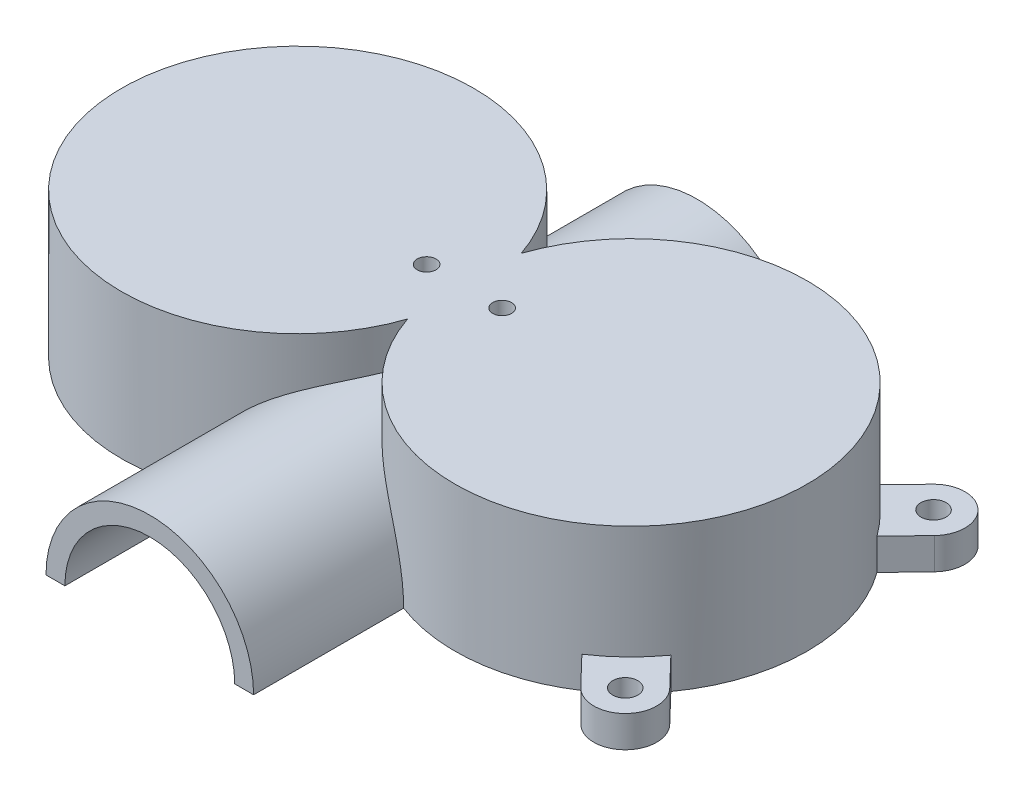
SolidWorks part; units mm, degrees
ref_plane "Front Plane" through (0, 0, 0) normal (0, 0, 1) x (1, 0, 0)
ref_plane "Top Plane" through (0, 0, 0) normal (0, 1, 0) x (1, 0, 0)
ref_plane "Right Plane" through (0, 0, 0) normal (1, 0, 0) x (0, 0, -1)
sketch "Sketch1" plane through (0, 0, 0) normal (0, 1, 0) x (1, 0, 0)
  line L0 (-26.5, 0) -> (26.5, 0) construction
  arc A0 (0, 9.0416) -> (0, -9.0416) centre (-26.5, 0) ccw
  arc A1 (0, -9.0416) -> (0, 9.0416) centre (26.5, 0) ccw
  dimension "D2" = 56
  dimension "D1" = 53
extrude "Boss-Extrude1" add sketch "Sketch1" along normal blind 23 contours A0 A1
shell "Shell1" [suppressed] thickness 3
sketch "Sketch2" plane through (0, 0, 0) normal (0, 1, 0) x (1, 0, 0)
  line L0 (-33.5, 33) -> (-33.5, 27.1109)
  line L1 (-23.5, 33) -> (-23.5, 27.8388)
  circle A0 centre (-28.5, 33) radius 2
  arc A1 (-23.5, 33) -> (-33.5, 33) centre (-28.5, 33) ccw
  arc A2 (-23.5, 27.8388) -> (-33.5, 27.1109) centre (-26.5, 0) ccw
  point P2 (0, 0)
  dimension "D3" = 4
  dimension "D4" = 10
  dimension "D5" = 56
  dimension "D1" = 33
  dimension "D2" = 28.5
  dimension "D6" = 26.5
extrude "Boss-Extrude2" add sketch "Sketch2" along normal blind 5
sketch "Sketch3" plane through (0, 0, 0) normal (0, 1, 0) x (1, 0, 0)
  line L0 (50.0744, 24.5) -> (50.0744, -24.5) construction
  line L1 (26.5, 0) -> (50.0744, -24.5) construction
  line L2 (0, 0) -> (50.0744, 0) construction
  line L3 (50.0744, 24.5) -> (26.5, 0) construction
  line L4 (46.4714, -27.9668) -> (41.9992, -23.319)
  line L5 (53.6773, -21.0332) -> (49.2051, -16.3854)
  line L6 (46.4714, 27.9668) -> (41.9992, 23.319)
  line L7 (53.6773, 21.0332) -> (49.2051, 16.3854)
  circle A0 centre (50.0744, 24.5) radius 2
  circle A1 centre (50.0744, -24.5) radius 2
  arc A2 (50.0744, 15.1079) -> (41.9992, 23.319) centre (26.5, 0) ccw
  arc A3 (53.6773, 21.0332) -> (46.4714, 27.9668) centre (50.0744, 24.5) ccw
  arc A4 (46.4714, -27.9668) -> (53.6773, -21.0332) centre (50.0744, -24.5) ccw
  arc A6 (41.9992, -23.319) -> (50.0744, -15.1079) centre (26.5, 0) ccw
  dimension "D3" = 56
  dimension "D5" = 4
  dimension "D6" = 10
  dimension "D1" = 49
  dimension "D2" = 26.5
  dimension "D4" = 34
extrude "Boss-Extrude3" add sketch "Sketch3" along normal blind 5 contours L7 A3 L6 A2 A0 | A6 L4 A4 L5 A1 region at (44.3687, 0, 25.5145) region at (53.4128, 0, -27.9695)
sketch "Sketch6" plane through (0, 0, 0) normal (0, 0, 1) x (1, 0, 0)
  line L0 (-16.5, 0) -> (16.5, 0)
  arc A0 (16.5, 0) -> (-16.5, 0) centre (0, 0) ccw
  dimension "D1" = 33
extrude "Boss-Extrude4" add sketch "Sketch6" against normal blind 37
extrude "Boss-Extrude5" add sketch "Sketch6<2>" along normal blind 50
sketch "Sketch6<2>" plane through (0, 0, 0) normal (0, 0, 1) x (1, 0, 0) same geometry as "Sketch6"
sketch "Sketch4" plane through (0, 0, 0) normal (0, 0, 1) x (1, 0, 0)
  line L0 (-13.5, 0) -> (13.5, 0)
  arc A0 (13.5, 0) -> (-13.5, 0) centre (0, 0) ccw
  dimension "D1" = 27
extrude "Cut-Extrude1" cut sketch "Sketch4" against normal through all both and the other way through all
sketch "Sketch5" plane through (0, 0, 0) normal (0, 1, 0) x (1, 0, 0)
  line L0 (26.5, 0) -> (-26.5, 0) construction
  circle A0 centre (-26.5, 0) radius 25
  circle A1 centre (26.5, 0) radius 25
  dimension "D2" = 50
  dimension "D1" = 53
extrude "Cut-Extrude4" cut sketch "Sketch5" along normal blind 20
sketch "Sketch7" plane through (0, 0, 0) normal (0, 1, 0) x (1, 0, 0)
  line L0 (-6, 0) -> (6, 0) construction
  circle A0 centre (-6, 0) radius 1.5
  circle A1 centre (6, 0) radius 1.5
  dimension "D1" = 3
  dimension "D2" = 12
extrude "Cut-Extrude6" cut sketch "Sketch7" along normal through all
